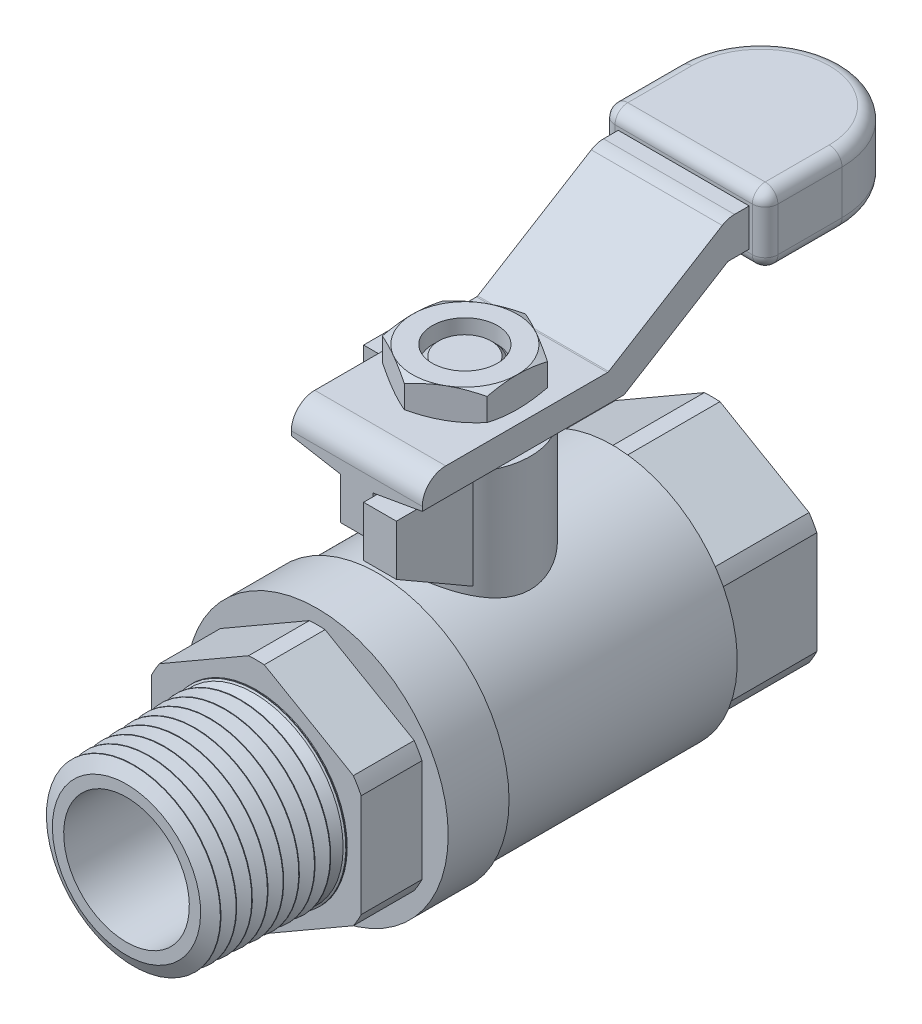
SolidWorks part; units mm, degrees
ref_plane "Front" through (0, 0, 0) normal (0, 0, 1) x (1, 0, 0)
ref_plane "Top" through (0, 0, 0) normal (0, 1, 0) x (1, 0, 0)
ref_plane "Right" through (0, 0, 0) normal (1, 0, 0) x (0, 0, -1)
sketch "Sketch1" plane through (0, -2.9295, 125.5668) normal (1, 0, 0) x (0, 0, -1)
  line L0 (139.5622, 2.9295) -> (139.5622, 11.7701)
  line L1 (139.5622, 11.7701) -> (140.4199, 13.3689) construction
  line L2 (140.4199, 13.3689) -> (141.3756, 11.8268) construction
  line L3 (141.3756, 11.8268) -> (142.2333, 13.4256) construction
  line L4 (142.2333, 13.4256) -> (143.189, 11.8835) construction
  line L5 (141.4083, 11.8877) -> (142.2006, 13.3646)
  line L6 (142.2006, 13.3646) -> (142.2697, 13.3668)
  line L7 (142.2697, 13.3668) -> (143.1526, 11.9422)
  line L8 (143.1526, 11.9422) -> (143.2217, 11.9444)
  line L9 (139.5622, 11.7701) -> (143.189, 11.8835) construction
  line L10 (140.4199, 13.3689) -> (142.2333, 13.4256) construction
  line L11 (139.9911, 12.5695) -> (142.7112, 12.6545) construction
  line L12 (139.5622, 2.9295) -> (125.5668, 2.9295) construction
  line L13 (143.2217, 11.9444) -> (144.014, 13.4213)
  line L14 (139.5949, 11.8311) -> (140.3872, 13.3079)
  line L15 (140.3872, 13.3079) -> (140.4563, 13.3101)
  line L16 (140.4563, 13.3101) -> (141.3392, 11.8856)
  line L17 (141.3392, 11.8856) -> (141.4083, 11.8877)
  line L18 (139.9911, 12.5695) -> (139.5622, 12.5561) construction
  line L19 (139.5622, 12.5561) -> (139.5622, 11.7701) construction
  line L20 (139.9911, -6.7105) -> (139.5622, -6.6971) construction
  line L21 (139.5949, 11.8311) -> (139.5622, 11.7701)
  line L22 (144.014, 13.4213) -> (144.0831, 13.4234)
  line L23 (144.0831, 13.4234) -> (144.966, 11.9989)
  line L24 (144.966, 11.9989) -> (145.0351, 12.0011)
  line L25 (145.0351, 12.0011) -> (145.8274, 13.478)
  line L26 (145.8274, 13.478) -> (145.8965, 13.4801)
  line L27 (145.8965, 13.4801) -> (146.7794, 12.0556)
  line L28 (146.7794, 12.0556) -> (146.8485, 12.0577)
  line L29 (146.8485, 12.0577) -> (147.6408, 13.5346)
  line L30 (147.6408, 13.5346) -> (147.7099, 13.5368)
  line L31 (147.7099, 13.5368) -> (148.5928, 12.1123)
  line L32 (148.5928, 12.1123) -> (148.6619, 12.1144)
  line L33 (148.6619, 12.1144) -> (149.4542, 13.5913)
  line L34 (149.4542, 13.5913) -> (149.5233, 13.5935)
  line L35 (149.5233, 13.5935) -> (150.4062, 12.1689)
  line L36 (150.4062, 12.1689) -> (150.4753, 12.1711)
  line L37 (150.4753, 12.1711) -> (151.2676, 13.648)
  line L38 (151.2676, 13.648) -> (151.3367, 13.6501)
  line L39 (151.3367, 13.6501) -> (152.2196, 12.2256)
  line L40 (152.2196, 12.2256) -> (152.2887, 12.2278)
  line L41 (152.2887, 12.2278) -> (153.081, 13.7046)
  line L42 (153.081, 13.7046) -> (153.1501, 13.7068)
  line L43 (153.1501, 13.7068) -> (154.033, 12.2823)
  line L44 (154.033, 12.2823) -> (154.1021, 12.2844)
  line L45 (154.1021, 12.2844) -> (154.8944, 13.7613)
  line L46 (154.8944, 13.7613) -> (154.9635, 13.7635)
  line L47 (154.9635, 13.7635) -> (155.8464, 12.3389)
  line L48 (155.8464, 12.3389) -> (155.9155, 12.3411)
  line L49 (155.9155, 12.3411) -> (156.7078, 13.818)
  line L50 (156.7078, 13.818) -> (156.7769, 13.8201)
  line L51 (156.7769, 13.8201) -> (157.6598, 12.3956)
  line L52 (157.6598, 12.3956) -> (157.7289, 12.3978)
  line L53 (157.7289, 12.3978) -> (158.5212, 13.8747)
  line L54 (158.5212, 13.8747) -> (158.5903, 13.8768)
  line L55 (158.5903, 13.8768) -> (159.4732, 12.4523)
  line L56 (159.4732, 12.4523) -> (159.5423, 12.4544)
  line L57 (159.5423, 12.4544) -> (160.3346, 13.9313)
  line L58 (160.3346, 13.9313) -> (160.4037, 13.9335)
  line L59 (160.4037, 13.9335) -> (161.2866, 12.509)
  line L60 (161.2866, 12.509) -> (161.3557, 12.5111)
  line L61 (161.3557, 12.5111) -> (162.148, 13.988)
  line L62 (162.148, 13.988) -> (162.2171, 13.9902)
  line L63 (162.2171, 13.9902) -> (163.1, 12.5656)
  line L64 (163.1, 12.5656) -> (163.1691, 12.5678)
  line L65 (163.1691, 12.5678) -> (163.9614, 14.0447)
  line L66 (163.9614, 14.0447) -> (164.0305, 14.0468)
  line L67 (164.0305, 14.0468) -> (164.9134, 12.6223)
  line L68 (164.9134, 12.6223) -> (164.9825, 12.6245)
  line L69 (164.9825, 12.6245) -> (165.7748, 14.1013)
  line L70 (165.7748, 14.1013) -> (165.8439, 14.1035)
  line L71 (165.8439, 14.1035) -> (166.7268, 12.679)
  line L72 (166.7268, 12.679) -> (166.7959, 12.6811)
  line L73 (139.5622, 2.9295) -> (166.7959, 2.9295)
  line L74 (166.7959, 2.9295) -> (166.7959, 12.6811)
  line L75 (140.4217, 13.309) -> (140.4199, 13.3689) construction
  line L76 (142.7112, 12.6545) -> (153.1258, 12.98) construction
  line L77 (153.1258, 12.98) -> (153.1258, 2.9295) construction
  line L78 (153.1258, 12.98) -> (155.0562, 13.0403) construction
  line L79 (155.0562, 13.0403) -> (155.0562, 2.9295) construction
  line L80 (125.5668, 2.9295) -> (85.2062, 2.9295) construction
  line L82 (85.2062, 2.9295) -> (85.2062, 13.0403) construction
  line L84 (153.1258, 12.2539) -> (155.0562, 12.3143) construction
  line L85 (139.5622, 7.3498) -> (125.5668, 7.3498) construction
  line L86 (125.5668, 7.3498) -> (125.5668, 2.9295) construction
  line L87 (155.0562, 13.0403) -> (85.2062, 13.0403) construction
  dimension "D1" = 60
  dimension "E0" = 19.2532
  dimension "Thread Pitch" = 1.8143
  dimension "D4" = 3.58
  dimension "L2 Thread Engagement" = 13.5636
  dimension "l Thread Length" = 15.494
  dimension "Body Length" = 69.85
  dimension "Right Length G" = 29.4894
  dimension "D5" = 54.356
revolve "Revolve1" add sketch "Sketch1" angle 360 about L12
sketch "Sketch6" plane through (0, 0, 0) normal (1, 0, 0) x (0, 0, -1)
  line L0 (29.4894, 0) -> (29.4894, 10.8369)
  line L1 (29.4894, 10.8369) -> (41.2291, 11.2038)
  line L2 (41.2291, 11.2038) -> (41.2291, 0)
  line L3 (41.2291, 0) -> (29.4894, 0)
  line L4 (29.4894, 10.1108) -> (29.4894, 0) construction
  line L5 (13.9954, 0) -> (41.2291, 0) construction
  line L6 (41.2291, 0) -> (41.2291, 9.7516) construction
  line L7 (31.1409, 10.8885) -> (31.2101, 10.8906) construction
revolve "Cut-Revolve3" cut sketch "Sketch6" angle 360 about L3
sketch "Sketch7" plane through (0, 0, 0) normal (1, 0, 0) x (0, 0, -1)
  line L0 (27.559, 9.3244) -> (29.4894, 10.8369)
  line L1 (29.4894, 10.8369) -> (29.4894, 9.3847)
  line L2 (29.4894, 9.3847) -> (27.559, 9.3244)
  line L3 (29.4894, 10.1108) -> (29.4894, 0) construction
  line L4 (14.8203, 10.3784) -> (14.8895, 10.3806) construction
  line L5 (27.559, 9.3244) -> (29.4894, 9.3847) construction
  line L6 (13.9954, 0) -> (27.559, 0) construction
  line L7 (27.559, 0) -> (27.559, 9.3244) construction
  line L8 (13.9954, 0) -> (13.9954, 8.8406) construction
  line L9 (0, 0) -> (13.9954, 0) construction
  line L10 (0, 0) -> (0, 7.493) construction
  line L11 (0, 7.493) -> (12.6478, 7.493) construction
  line L12 (13.9954, 0) -> (13.9954, 8.8406) construction
  line L13 (13.9954, 8.8406) -> (12.6478, 7.493) construction
  dimension "D1" = 45
  dimension "Min ID" = 14.986
revolve "Revolve3" add sketch "Sketch7" angle 360 about L6
pattern_linear "LPattern2" count 2 spacing 54.356 along (0, 0, 1) of bodies 114
sketch "Sketch30" plane through (0, 0, 0) normal (1, 0, 0) x (0, 0, -1)
  line L0 (-40.3606, 0) -> (-40.3606, 10.1108) construction
  line L1 (-40.3606, 7.493) -> (0, 7.493)
  line L2 (-40.3606, 7.493) -> (-40.3606, 0)
  line L3 (-40.3606, 0) -> (0, 0)
  line L4 (0, 7.493) -> (0, 0)
  line L5 (0, 7.493) -> (12.6478, 7.493) construction
  line L6 (13.9954, 0) -> (0, 0) construction
  line L7 (0, 4.4203) -> (0, 0) construction
revolve "Cut-Revolve8" cut sketch "Sketch30" angle 360 about L3
sketch "Sketch29" plane through (0, 0, 0) normal (1, 0, 0) x (0, 0, -1)
  line L0 (0, 0) -> (13.9954, 0) construction
  line L1 (13.9954, 0) -> (13.9954, 8.8406) construction
  line L2 (0, 7.493) -> (12.6478, 7.493) construction
  line L3 (13.9954, 8.8406) -> (12.6478, 7.493) construction
  line L4 (-24.8666, 0) -> (13.9954, 0)
  line L5 (13.9954, 0) -> (13.9954, 8.8406)
  line L6 (-24.8666, 7.493) -> (12.6478, 7.493)
  line L7 (13.9954, 8.8406) -> (12.6478, 7.493)
  line L8 (-24.8666, -10.8369) -> (-24.8666, 10.8369) construction
  line L9 (-24.8666, 0) -> (-24.8666, 7.493)
revolve "Revolve6" add sketch "Sketch29" angle 360 about L4
sketch "Sketch8" plane through (0, 0, 24.8666) normal (0, 0, 1) x (1, 0, 0)
  line L1 (0, 14.4301) -> (-12.4968, 7.215)
  line L2 (-12.4968, 7.215) -> (-12.4968, -7.215)
  line L3 (-12.4968, -7.215) -> (0, -14.4301)
  line L4 (0, -14.4301) -> (12.4968, -7.215)
  line L5 (12.4968, -7.215) -> (12.4968, 7.215)
  line L6 (12.4968, 7.215) -> (0, 14.4301)
  circle A0 centre (0, 0) radius 12.4968 construction
  dimension "Body Hex" = 24.9936
extrude "Extrude1" add sketch "Sketch8" against normal up to surface (54.356 mm away) separate body up to face at (10.8369, 0, -29.4894)
sketch "Sketch9" plane through (0, 0, 0) normal (1, 0, 0) x (0, 0, -1)
  line L0 (-17.6095, 7.215) -> (-17.6095, 15.621)
  line L1 (-17.6095, 15.621) -> (-10.3523, 15.621)
  line L2 (-10.3523, 15.621) -> (-10.3523, 15.1811)
  line L3 (-10.3523, 15.1811) -> (-10.0412, 14.87)
  line L4 (-10.0412, 14.87) -> (17.624, 14.87)
  line L5 (17.624, 14.87) -> (17.624, 7.215)
  line L6 (17.624, 7.215) -> (-17.6095, 7.215)
  line L7 (29.4894, 7.215) -> (-24.8666, 7.215) construction
  line L8 (0, 0) -> (0, 7.215) construction
  line L9 (13.9954, 0) -> (13.9954, 8.8406) construction
  line L10 (0, 0) -> (-17.6095, 0) construction
  line L11 (-17.6095, 0) -> (-17.6095, 7.215) construction
  line L12 (-10.0412, 14.87) -> (-10.0412, 14.4301) construction
  line L13 (29.4894, 14.4301) -> (-24.8666, 14.4301) construction
  line L14 (29.4894, 10.1108) -> (29.4894, 14.87) construction
  line L15 (29.4894, 14.87) -> (17.624, 14.87) construction
  line L16 (-24.8666, 14.4301) -> (-24.8666, 15.621) construction
  line L17 (-24.8666, 15.621) -> (-17.6095, 15.621) construction
  dimension "D1" = 3.6286
  dimension "D2" = 31.242
  dimension "D3" = 135
  dimension "D4" = 7.2571
revolve "Revolve4" add sketch "Sketch9" angle 360 about L10
sketch "Sketch10" plane through (0, 0, 0) normal (1, 0, 0) x (0, 0, -1)
  line L0 (0, 7.493) -> (0, 23.8567)
  line L1 (3.8925, 26.4221) -> (3.9179, 26.4221) construction
  line L2 (7.8105, 26.4221) -> (7.8105, 7.493)
  line L3 (7.8105, 7.493) -> (0, 7.493)
  line L4 (0, 0) -> (0, 7.493) construction
  line L5 (-9.0805, 21.1485) -> (-9.0805, 26.6761) construction
  line L6 (-9.0805, 26.6761) -> (10.3505, 26.6761) construction
  line L7 (10.3505, 26.6761) -> (23.5567, 34.7738) construction
  line L8 (-9.0805, 21.1485) -> (-12.8905, 21.1485) construction
  line L9 (-12.8905, 21.1485) -> (-12.8905, 30.4861) construction
  line L10 (-12.8905, 30.4861) -> (9.2754, 30.4861) construction
  line L11 (9.2754, 30.4861) -> (23.5567, 39.243) construction
  line L12 (23.5567, 39.243) -> (23.5567, 34.7738) construction
  line L13 (17.624, 14.87) -> (-10.0412, 14.87) construction
  line L14 (23.5567, 41.148) -> (23.5567, 32.8688) construction
  line L15 (23.5567, 32.8688) -> (44.9834, 32.8688) construction
  line L16 (44.9834, 32.8688) -> (44.9834, 41.148) construction
  line L17 (44.9834, 41.148) -> (23.5567, 41.148) construction
  line L18 (-1.8075, 30.4861) -> (-1.8075, 26.6761) construction
  line L19 (16.416, 34.8645) -> (18.4076, 31.6165) construction
  line L20 (-7.8105, 26.4221) -> (-7.8105, 7.493) construction
  line L21 (0, 7.493) -> (12.6478, 7.493) construction
  line L22 (23.5567, 32.8688) -> (23.5567, 14.87) construction
  line L23 (29.4894, 14.87) -> (17.624, 14.87) construction
  line L24 (-10.3523, 15.621) -> (-10.3523, 21.1485) construction
  line L25 (-10.3523, 21.1485) -> (-12.8905, 21.1485) construction
  line L26 (3.8925, 26.4221) -> (3.8925, 32.8688)
  line L27 (3.8925, 32.8688) -> (0, 32.8688)
  line L28 (3.8925, 26.4221) -> (3.8925, 23.8821)
  line L29 (3.8925, 23.8821) -> (0, 23.8821)
  line L30 (0, 23.8567) -> (3.9179, 23.8567)
  line L31 (3.9179, 23.8567) -> (3.9179, 26.4221)
  line L32 (3.9179, 26.4221) -> (7.8105, 26.4221)
  line L33 (0, 23.8567) -> (0, 23.8821) construction
  line L34 (0, 23.8821) -> (0, 32.8688)
  line L35 (-3.8925, 26.4221) -> (-3.8925, 32.8688) construction
  line L36 (3.9179, 23.8567) -> (3.9179, 14.87) construction
  line L37 (3.9179, 14.87) -> (23.5567, 14.87) construction
  point P26 (23.5567, 37.0084)
  dimension "Handle Height" = 41.148
  dimension "Handle Length" = 44.9834
  dimension "D3" = 15.621
  dimension "D5" = 17.9988
  dimension "D6" = 3.81
  dimension "D7" = 1.27
  dimension "D8" = 0.254
  dimension "D9" = 2.54
  dimension "D11" = 0.0254
  dimension "D12" = 0.0254
  dimension "D13" = 8.9867
  dimension "D14" = 2.54
  dimension "D2" = 1.905
revolve "Revolve5" add sketch "Sketch10" angle 360 about L4
chamfer "Chamfer1" distance 0.762 angle 45 1 edges at (0, 32.8688, -3.8925)
sketch "Sketch20" plane through (0, 0, 0) normal (1, 0, 0) x (0, 0, -1)
  line L0 (3.8925, 32.8688) -> (-3.8926, 32.8688) construction
  line L1 (-3.8926, 32.8688) -> (-3.8925, 32.075) construction
  line L2 (-3.8925, 32.075) -> (3.8925, 32.8688) construction
  line L3 (3.8925, 32.8688) -> (3.9026, 32.7701) construction
  line L4 (3.9026, 32.7701) -> (3.9731, 32.0791)
  line L5 (3.9731, 32.0791) -> (3.5205, 32.2823)
  line L6 (3.5205, 32.2823) -> (3.5004, 32.4797)
  line L7 (3.5004, 32.4797) -> (3.9026, 32.7701)
  line L8 (3.5104, 32.381) -> (3.9378, 32.4246) construction
  line L9 (3.8925, 32.8688) -> (3.8926, 32.42) construction
  line L10 (3.8926, 32.42) -> (-3.8925, 31.6262) construction
  line L11 (-3.8925, 31.6262) -> (-3.8925, 32.075) construction
  line L12 (-0.0862, 32.8688) -> (0.0862, 31.1774) construction
  line L13 (-3.8925, 26.4221) -> (-3.8925, 32.8688) construction
  line L14 (3.8925, 26.4221) -> (3.8925, 32.8688) construction
  line L15 (3.8925, 32.8688) -> (0, 32.8688) construction
  point P13 (0, 32.0231)
  dimension "D2" = 0.1984
  dimension "D3" = 0.7937
  dimension "D4" = 60
  dimension "D5" = 0.7937
revolve "Cut-Revolve6" cut sketch "Sketch20" angle 360 about L12
pattern_linear "LPattern1" count 2 spacing 0.7937 along (0, 1, 0) count 11 spacing 0.7937 along (0, -1, 0) of "Cut-Revolve6"
sketch "Sketch26" plane through (0, 23.8567, 0) normal (0, 1, 0) x (-1, 0, 0)
  circle A1 centre (0, 0) radius 3.9179
  circle A2 centre (0, 0) radius 3.9179
  dimension "D1" = 0
extrude "Extrude8" add sketch "Sketch26" along normal blind 0.127
sketch "Sketch16" plane through (0, 0, 0) normal (1, 0, 0) x (0, 0, -1)
  line L0 (-24.8666, 7.215) -> (-24.8666, 14.4301) construction
  line L1 (29.4894, 14.4301) -> (17.624, 14.4301)
  line L2 (29.4894, 14.4301) -> (29.4894, 13.9221)
  line L3 (29.4894, 13.9221) -> (17.624, 13.9221)
  line L4 (17.624, 14.4301) -> (17.624, 13.9221)
  line L5 (-24.8666, 14.4301) -> (-17.6095, 14.4301)
  line L6 (-24.8666, 14.4301) -> (-24.8666, 13.9221)
  line L7 (-24.8666, 13.9221) -> (-17.6095, 13.9221)
  line L8 (-17.6095, 14.4301) -> (-17.6095, 13.9221)
  line L9 (29.4894, 14.4301) -> (29.4894, 7.215) construction
  line L10 (17.624, -14.87) -> (17.624, 14.87) construction
  line L11 (-17.6095, 15.621) -> (-17.6095, -15.621) construction
  line L12 (-17.6095, 14.4301) -> (-24.8666, 14.4301) construction
  line L13 (0, 0) -> (-24.8666, 0) construction
  line L14 (-24.8666, 0) -> (-24.8666, 13.9221) construction
  dimension "D1" = 0.508
revolve "Cut-Revolve5" cut sketch "Sketch16" angle 360 about L13
combine bodies "Combine1" operation type subtract main body 126 bodies to subtract 151
combine bodies "Combine2" operation type add bodies to combine 150 123
sketch "Sketch11" plane through (0, 0, 0) normal (1, 0, 0) x (0, 0, -1)
  line L1 (9.2754, 30.4861) -> (23.5567, 39.243) construction
  line L2 (10.3505, 26.6761) -> (23.5567, 34.7738) construction
  line L3 (-9.0805, 26.6761) -> (10.3505, 26.6761) construction
  line L4 (-9.0805, 21.1485) -> (-9.0805, 26.6761) construction
  line L5 (-12.8905, 30.4861) -> (9.2754, 30.4861) construction
  line L6 (-12.8905, 21.1485) -> (-12.8905, 30.4861) construction
  line L7 (43.0784, 34.7738) -> (43.0784, 39.243)
  line L8 (9.2754, 30.4861) -> (23.5567, 39.243)
  line L9 (10.3505, 26.6761) -> (23.5567, 34.7738)
  line L10 (-9.0805, 26.6761) -> (10.3505, 26.6761)
  line L11 (-9.0805, 21.1485) -> (-9.0805, 26.6761)
  line L12 (-12.8905, 30.4861) -> (9.2754, 30.4861)
  line L13 (-12.8905, 21.1485) -> (-12.8905, 30.4861)
  line L14 (-9.0805, 21.1485) -> (-12.8905, 21.1485) construction
  line L15 (-9.0805, 21.1485) -> (-12.8905, 21.1485)
  line L16 (23.5567, 39.243) -> (43.0784, 39.243)
  line L17 (23.5567, 34.7738) -> (43.0784, 34.7738)
  line L18 (44.9834, 32.8688) -> (44.9834, 41.148) construction
  dimension "D1" = 1.905
extrude "Extrude2" add sketch "Sketch11" along normal mid plane 15.621 separate body
sketch "Sketch21" plane through (0, 30.4861, 0) normal (0, 1, 0) x (-1, 0, 0)
  circle A0 centre (0, 0) radius 3.918
extrude "Cut-Extrude1" cut sketch "Sketch21" against normal through all
fillet "Fillet1" radius 0.254 3 edges at (0, 34.7738, -23.5567) (0, 30.4861, -9.2754) (0, 26.6761, 9.0805)
fillet "Fillet2" radius 2.794 3 edges at (0, 30.4861, 12.8905) (0, 39.243, -23.5567) (0, 26.6761, -10.3505)
fillet "Fillet3" radius 7.8105 2 edges at (-7.8105, 37.0084, -43.0784) (7.8105, 37.0084, -43.0784)
sketch "Sketch12" plane through (0, 39.243, 0) normal (0, 1, 0) x (-1, 0, 0)
  line L0 (9.7155, -26.0967) -> (-9.7155, -26.0967)
  line L1 (-9.7155, -26.0967) -> (-9.7155, -35.2679)
  line L2 (9.7155, -35.2679) -> (9.7155, -26.0967)
  line L3 (-7.8105, -35.2679) -> (-7.8105, -24.3451) construction
  line L4 (0, -44.9834) -> (0, -23.5567) construction
  arc A0 (-9.7155, -35.2679) -> (9.7155, -35.2679) centre (0, -35.2679) ccw
  arc A1 (-7.8105, -35.2679) -> (0, -43.0784) centre (0, -35.2679) ccw construction
  dimension "D1" = 1.905
  dimension "D2" = 2.54
extrude "Extrude3" add sketch "Sketch12" along normal blind 1.905 separate body
sketch "Sketch13" plane through (0, 34.7738, 0) normal (0, -1, 0) x (1, 0, 0)
  line L3 (9.7155, -26.0967) -> (-9.7155, -26.0967)
  line L4 (9.7155, -35.2679) -> (9.7155, -26.0967)
  line L5 (-9.7155, -26.0967) -> (-9.7155, -35.2679)
  line L6 (9.7155, -26.0967) -> (-9.7155, -26.0967)
  line L7 (9.7155, -35.2679) -> (9.7155, -26.0967)
  line L8 (-9.7155, -26.0967) -> (-9.7155, -35.2679)
  arc A1 (-9.7155, -35.2679) -> (9.7155, -35.2679) centre (0, -35.2679) ccw
  arc A2 (-9.7155, -35.2679) -> (9.7155, -35.2679) centre (0, -35.2679) ccw
  dimension "D1" = 0
extrude "Extrude4" add sketch "Sketch13" along normal blind 1.905 separate body
sketch "Sketch14" plane through (0, 39.243, 0) normal (0, -1, 0) x (1, 0, 0)
  line L0 (-7.8105, -35.2679) -> (-7.8105, -24.3451) construction
  line L1 (7.8105, -35.2679) -> (7.8105, -24.3451) construction
  line L2 (-7.8105, -35.2679) -> (-7.8105, -26.0967)
  line L3 (9.7155, -26.0967) -> (-9.7155, -26.0967)
  line L4 (9.7155, -35.2679) -> (9.7155, -26.0967)
  line L5 (-9.7155, -26.0967) -> (-9.7155, -35.2679)
  line L6 (9.7155, -26.0967) -> (7.8105, -26.0967)
  line L7 (9.7155, -35.2679) -> (9.7155, -26.0967)
  line L8 (-9.7155, -26.0967) -> (-9.7155, -35.2679)
  line L9 (7.8105, -35.2679) -> (7.8105, -26.0967)
  line L10 (-7.8105, -26.0967) -> (-9.7155, -26.0967)
  arc A0 (-7.8105, -35.2679) -> (0, -43.0784) centre (0, -35.2679) ccw construction
  arc A1 (-9.7155, -35.2679) -> (9.7155, -35.2679) centre (0, -35.2679) ccw
  arc A2 (-9.7155, -35.2679) -> (9.7155, -35.2679) centre (0, -35.2679) ccw
  arc A3 (0, -43.0784) -> (7.8105, -35.2679) centre (0, -35.2679) ccw construction
  arc A4 (-7.8105, -35.2679) -> (0, -43.0784) centre (0, -35.2679) ccw
  arc A5 (0, -43.0784) -> (7.8105, -35.2679) centre (0, -35.2679) ccw
  dimension "D1" = 0
extrude "Extrude5" add sketch "Sketch14" along normal up to surface (4.4692 mm away) up to face at (0, 34.7738, -33.1112)
fillet "Fillet4" radius 1.524 10 edges at (-9.7155, 41.148, -30.6823) (0, 41.148, -44.9834) (-9.7155, 32.8688, -30.6823) (0, 32.8688, -44.9834) (9.7155, 41.148, -30.6823) (9.7155, 32.8688, -30.6823) (9.7155, 37.0084, -26.0967) (-9.7155, 37.0084, -26.0967) (0, 41.148, -26.0967) (0, 32.8688, -26.0967)
sketch "Sketch15" plane through (0, 30.4861, 0) normal (0, 1, 0) x (-1, 0, 0)
  line L1 (0, 7.215) -> (-6.2484, 3.6075)
  line L2 (-6.2484, 3.6075) -> (-6.2484, -3.6075)
  line L3 (-6.2484, -3.6075) -> (0, -7.215)
  line L4 (0, -7.215) -> (6.2484, -3.6075)
  line L5 (6.2484, -3.6075) -> (6.2484, 3.6075)
  line L6 (6.2484, 3.6075) -> (0, 7.215)
  circle A0 centre (0, 0) radius 6.2484 construction
  dimension "D1" = 12.4968
extrude "Extrude6" add sketch "Sketch15" along normal blind 3.5947 separate body
sketch "Sketch22" plane through (0, 0, 0) normal (1, 0, 0) x (0, 0, -1)
  line L0 (6.2484, 34.0808) -> (7.215, 34.0808)
  line L1 (0, 34.0808) -> (3.8925, 34.0808)
  line L2 (0, 34.0808) -> (0, 30.4861)
  line L3 (0, 30.4861) -> (3.8925, 30.4861)
  line L4 (3.8925, 34.0808) -> (3.8925, 30.4861)
  line L5 (7.215, 34.0808) -> (7.215, 33.63)
  line L6 (7.215, 33.63) -> (6.2484, 34.0808)
  line L7 (6.2484, 30.4861) -> (7.215, 30.4861)
  line L8 (7.215, 30.4861) -> (7.215, 30.9368)
  line L9 (7.215, 30.9368) -> (6.2484, 30.4861)
  line L10 (7.215, 34.0808) -> (7.215, 30.4861) construction
  line L11 (3.6075, 34.0808) -> (7.215, 34.0808) construction
  line L12 (-12.8905, 30.4861) -> (9.2754, 30.4861) construction
  line L13 (0, 23.8821) -> (0, 32.8688) construction
  line L14 (3.8925, 26.4221) -> (3.8925, 32.8688) construction
  line L15 (0, 0) -> (0, 30.4861) construction
  line L16 (6.2484, 30.4861) -> (6.2484, 34.0808) construction
  dimension "D1" = 25
  dimension "D2" = 12.4968
revolve "Cut-Revolve7" cut sketch "Sketch22" angle 360 about L15
sketch "Sketch23" plane through (0, 0, 12.8905) normal (0, 0, 1) x (1, 0, 0)
  line L0 (-7.8105, 27.1841) -> (-1.9526, 26.1512)
  line L1 (-1.9526, 26.1512) -> (-1.9526, 21.1485)
  line L2 (-1.9526, 21.1485) -> (1.9526, 21.1485)
  line L3 (1.9526, 21.1485) -> (1.9526, 26.1512)
  line L4 (1.9526, 26.1512) -> (7.8105, 27.1841)
  line L5 (7.8105, 27.1841) -> (7.8105, 19.8785)
  line L6 (7.8105, 19.8785) -> (-7.8105, 19.8785)
  line L7 (-7.8105, 19.8785) -> (-7.8105, 27.1841)
  line L8 (-1.9526, 21.1485) -> (-7.8105, 21.1485) construction
  line L9 (1.9526, 21.1485) -> (7.8105, 21.1485) construction
  line L10 (0, 21.1485) -> (0, 19.8785) construction
  line L11 (-7.8105, 27.1841) -> (7.8105, 27.1841) construction
  line L12 (-1.9526, 26.1512) -> (1.9526, 26.1512) construction
  line L13 (-7.8105, 27.6921) -> (-7.8105, 21.1485) construction
  line L14 (7.8105, 27.6921) -> (7.8105, 21.1485) construction
  line L15 (7.8105, 21.1485) -> (-7.8105, 21.1485) construction
  line L16 (7.8105, 27.6921) -> (-7.8105, 27.6921) construction
  dimension "D1" = 3.9052
  dimension "D2" = 10
  dimension "D3" = 0.508
  dimension "D4" = 1.27
  dimension "D5" = 15.621
extrude "Cut-Extrude2" cut sketch "Sketch23" against normal through all
sketch "Sketch24" plane through (0, 0, 12.8905) normal (0, 0, 1) x (1, 0, 0)
  line L0 (-1.9526, 26.1512) -> (1.9526, 26.1512) construction
  line L1 (2.0796, 25.8972) -> (5.9849, 25.8972)
  line L2 (2.0796, 25.8972) -> (2.0796, 19.8785)
  line L3 (2.0796, 19.8785) -> (5.9849, 19.8785)
  line L4 (5.9849, 25.8972) -> (5.9849, 19.8785)
  line L6 (-1.9526, 21.1485) -> (1.9526, 21.1485) construction
  line L8 (1.9526, 21.1485) -> (1.9526, 26.1512) construction
  dimension "D1" = 0.254
  dimension "D3" = 1.27
  dimension "D2" = 0.127
  dimension "D4" = 3.9052
extrude "Extrude7" add sketch "Sketch24" along normal blind 1.27 and the other way up to surface other way up to face at (0.692, 14.8539, 7.7798)
ref_axis "Axis1" through (0, -15.2056, 0) along (0, 1, 0)
ref_plane "Plane1" through (0, 0, 0) normal (-0.7071, 0, -0.7071) x (-0.7071, 0, 0.7071)
mirror "Mirror3" about plane through (0, 0, 0) normal (-0.7071, 0, -0.7071) of "Extrude7"
draft "Draft1" type of draft neutral plane draft angle 30 faces to draft 1 face at (4.0799, 19.8785, 10.2912) neutral plane through (2.0796, 19.8785, 14.1605) neutral plane normal (0, 0, 1) parameters "D1"=30
draft "Draft2" type of draft neutral plane draft angle 30 faces to draft 1 face at (-10.2912, 19.8785, -4.0799) neutral plane through (-14.1605, 19.8785, -2.0796) neutral plane normal (-1, 0, 0) parameters "D1"=30
equation "\"D2@Sketch1\"=\"Thread Pitch@Sketch1\"*.033"
equation "\"D2@Sketch9\"=\"Body Hex@Sketch8\"*1.25"
equation "\"D1@Sketch9\" = \"Thread Pitch@Sketch1\"*2"
equation "\"D4@Sketch9\"=\"D1@Sketch9\"*2"
equation "\"D3@Sketch10\"=\"Body Hex@Sketch8\"*.625"
equation "\"D1@Extrude2\"=\"D3@Sketch10\""
equation "\"D1@Fillet3\"=\"D1@Extrude2\"/2"
equation "\"D1@Sketch15\"=\"D1@Extrude2\"*.8"
equation "\"D2@LPattern1\"=\"D13@Sketch10\"/\"D3@Sketch20\""
equation "\"D2@Sketch22\"=\"D1@Sketch15\""
equation "\"D1@Extrude6\"=\"D13@Sketch10\"/2.5"
equation "\"D1@Sketch23\"=\"D5@Sketch23\"/4"
equation "\"D4@Sketch24\"=\"D1@Sketch23\""
equation "\"D3@LPattern2\"=\"D5@Sketch1\""
